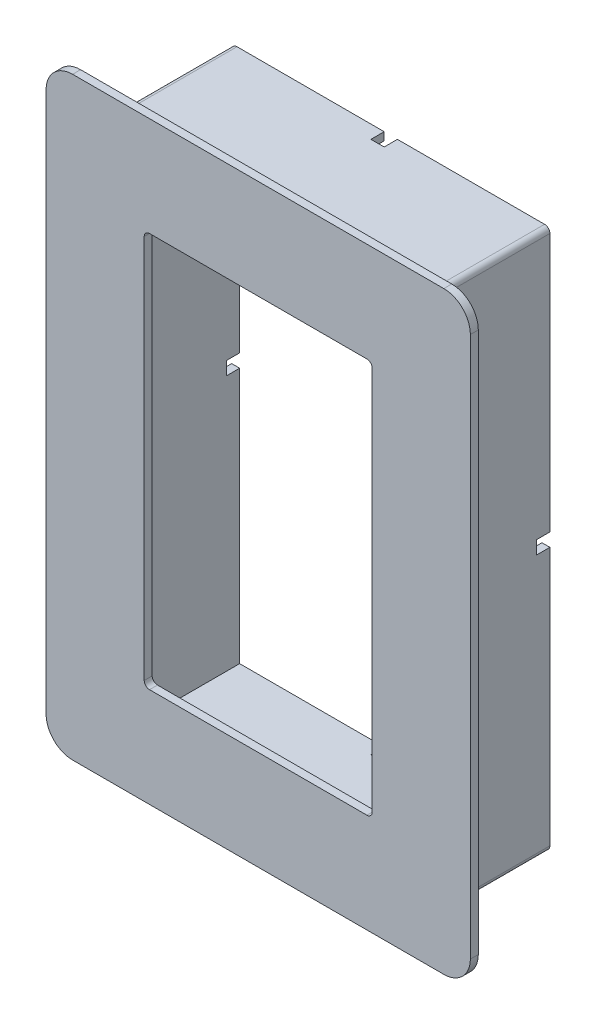
SolidWorks part; units mm, degrees
ref_plane "Plano frontal" through (0, 0, 0) normal (0, 0, 1) x (1, 0, 0)
ref_plane "Plano superior" through (0, 0, 0) normal (0, 1, 0) x (1, 0, 0)
ref_plane "Plano direito" through (0, 0, 0) normal (1, 0, 0) x (0, 0, -1)
sketch "Esboço1" plane through (0, 0, 0) normal (0, 0, 1) x (1, 0, 0)
  line L5 (-32.6754, 150.8202) -> (87.3246, 150.8202)
  line L6 (-32.6754, 150.8202) -> (-32.6754, -53.1798)
  line L7 (-32.6754, -53.1798) -> (87.3246, -53.1798)
  line L8 (87.3246, 150.8202) -> (87.3246, -53.1798)
  dimension "D1" = 120
  dimension "D2" = 204
extrude "Ressalto-extrusão1" add sketch "Esboço1" along normal blind 50
sketch "Esboço2" plane through (0, 0, 0) normal (0, 0, -1) x (-1, 0, 0)
  line L0 (32.6754, -53.1798) -> (-87.3246, -53.1798) construction
  line L1 (29.6754, -50.1798) -> (-84.3246, -50.1798)
  line L2 (29.6754, -50.1798) -> (29.6754, 147.8202)
  line L3 (29.6754, 147.8202) -> (-84.3246, 147.8202)
  line L4 (-84.3246, -50.1798) -> (-84.3246, 147.8202)
  line L5 (-87.3246, -53.1798) -> (-87.3246, 150.8202) construction
  line L6 (32.6754, 150.8202) -> (32.6754, -53.1798) construction
  line L7 (-87.3246, 150.8202) -> (32.6754, 150.8202) construction
  dimension "D1" = 3
  dimension "D2" = 3
  dimension "D3" = 3
  dimension "D4" = 3
extrude "Corte-extrusão1" cut sketch "Esboço2" against normal blind 47
sketch "Esboço4" plane through (0, 0, 50) normal (0, 0, 1) x (1, 0, 0)
  line L1 (-15.6754, 123.3202) -> (70.3246, 123.3202)
  line L2 (-15.6754, 123.3202) -> (-15.6754, -25.6798)
  line L3 (-15.6754, -25.6798) -> (70.3246, -25.6798)
  line L4 (70.3246, 123.3202) -> (70.3246, -25.6798)
  line L5 (-32.6754, -53.1798) -> (87.3246, -53.1798) construction
  line L7 (-32.6754, 150.8202) -> (-32.6754, -53.1798) construction
  dimension "D1" = 86
  dimension "D2" = 27.5
  dimension "D3" = 149
  dimension "D4" = 17
extrude "Corte-extrusão2" cut sketch "Esboço4" against normal blind 45 contours L2 L3 L4 L1
sketch "Esboço7" plane through (87.3246, 0, 0) normal (1, 0, 0) x (0, 0, -1)
  line L0 (-50, -53.1798) -> (-50, 150.8202) construction
  line L1 (-50, 150.8202) -> (-47, 150.8202)
  line L2 (-50, 150.8202) -> (-50, -53.1798)
  line L3 (-50, -53.1798) -> (-47, -53.1798)
  line L4 (-47, 150.8202) -> (-47, -53.1798)
  line L5 (-50, 150.8202) -> (0, 150.8202) construction
  line L6 (-50, -53.1798) -> (0, -53.1798) construction
  dimension "D1" = 3
extrude "Ressalto-extrusão2" add sketch "Esboço7" along normal blind 20 contours L2 L3 L4 L1
sketch "Esboço12" plane through (-32.6754, 0, 0) normal (-1, 0, 0) x (0, 0, 1)
  line L0 (50, -53.1798) -> (0, -53.1798) construction
  line L1 (50, 150.8202) -> (47, 150.8202)
  line L2 (50, 150.8202) -> (50, -53.1798)
  line L3 (50, -53.1798) -> (47, -53.1798)
  line L4 (47, 150.8202) -> (47, -53.1798)
  dimension "D1" = 3
extrude "Ressalto-extrusão3" add sketch "Esboço12" along normal blind 20 contours L2 L3 L4 L1
sketch "Esboço13" plane through (0, 150.8202, 0) normal (0, 1, 0) x (1, 0, 0)
  line L1 (107.3246, -47) -> (-52.6754, -47)
  line L2 (107.3246, -47) -> (107.3246, -50)
  line L3 (107.3246, -50) -> (-52.6754, -50)
  line L4 (-52.6754, -47) -> (-52.6754, -50)
extrude "Ressalto-extrusão4" add sketch "Esboço13" along normal blind 10 contours L3 L4 L1 L2
sketch "Esboço14" plane through (0, -53.1798, 0) normal (0, -1, 0) x (1, 0, 0)
  line L1 (-52.6754, 50) -> (107.3246, 50)
  line L2 (-52.6754, 50) -> (-52.6754, 47)
  line L3 (-52.6754, 47) -> (107.3246, 47)
  line L4 (107.3246, 50) -> (107.3246, 47)
extrude "Ressalto-extrusão5" add sketch "Esboço14" along normal blind 10
fillet "Filete1" radius 10 1 edges at (107.3246, 160.8202, 48.5)
sketch "Esboço15" plane through (0, 0, 0) normal (0, 0, -1) x (-1, 0, 0)
  line L0 (32.6754, 150.8202) -> (32.6754, -53.1798) construction
  line L1 (32.6754, 51.3202) -> (29.6754, 51.3202)
  line L2 (32.6754, 51.3202) -> (32.6754, 46.3202)
  line L3 (32.6754, 46.3202) -> (29.6754, 46.3202)
  line L4 (29.6754, 51.3202) -> (29.6754, 46.3202)
  line L5 (29.6754, -50.1798) -> (29.6754, 147.8202) construction
  line L6 (29.6754, 147.8202) -> (-84.3246, 147.8202) construction
  line L7 (-24.8246, 147.8202) -> (-29.8246, 147.8202)
  line L8 (-24.8246, 147.8202) -> (-24.8246, 150.8202)
  line L9 (-24.8246, 150.8202) -> (-29.8246, 150.8202)
  line L10 (-29.8246, 147.8202) -> (-29.8246, 150.8202)
  line L11 (-87.3246, 150.8202) -> (32.6754, 150.8202) construction
  line L12 (32.6754, -53.1798) -> (-87.3246, -53.1798) construction
  line L13 (-24.8246, -53.1798) -> (-29.8246, -53.1798)
  line L14 (-24.8246, -53.1798) -> (-24.8246, -50.1798)
  line L15 (-24.8246, -50.1798) -> (-29.8246, -50.1798)
  line L16 (-29.8246, -53.1798) -> (-29.8246, -50.1798)
  line L18 (-84.3246, 147.8202) -> (-84.3246, -50.1798) construction
  line L19 (-84.3246, 51.3202) -> (-87.3246, 51.3202)
  line L20 (-84.3246, 51.3202) -> (-84.3246, 46.3202)
  line L21 (-84.3246, 46.3202) -> (-87.3246, 46.3202)
  line L22 (-87.3246, 51.3202) -> (-87.3246, 46.3202)
  line L23 (-87.3246, -53.1798) -> (-87.3246, 150.8202) construction
  dimension "D1" = 5
  dimension "D2" = 5
  dimension "D3" = 5
  dimension "D4" = 5
  dimension "D5" = 57.5
  dimension "D6" = 99.5
  dimension "D7" = 99.5
  dimension "D8" = 57.5
extrude "Corte-extrusão4" cut sketch "Esboço15" against normal blind 5 contours L9 L10 L7 L8 | L2 L3 L4 L1 | L13 L16 L15 L14 | L22 L21 L20 L19
fillet "Filete2" radius 10 1 edges at (-52.6754, 160.8202, 48.5)
fillet "Filete3" radius 10 1 edges at (107.3246, -63.1798, 48.5)
fillet "Filete4" radius 10 1 edges at (-52.6754, -63.1798, 48.5)
fillet "Filete5" radius 2 1 edges
fillet "Filete6" radius 2 3 edges
fillet "Filete8" radius 2 4 edges at (70.3246, 123.3202, 48.5) (70.3246, -25.6798, 48.5) (-15.6754, -25.6798, 48.5) (-15.6754, 123.3202, 48.5)
